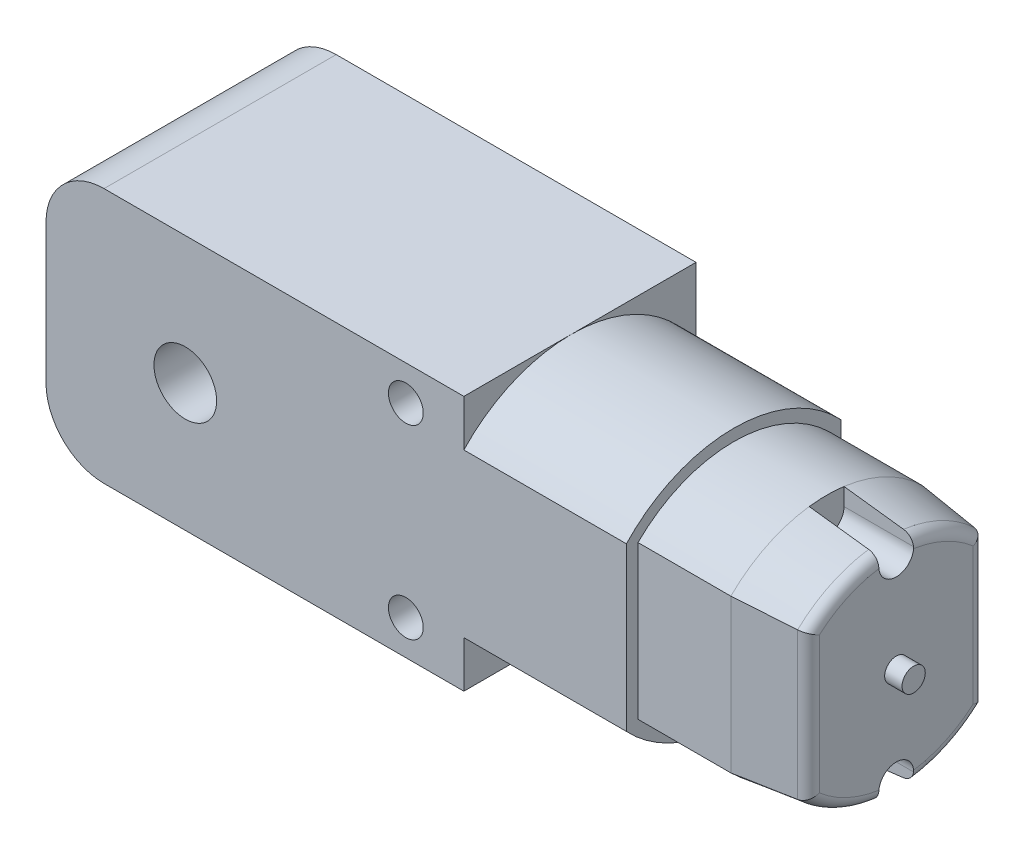
SolidWorks part; units mm, degrees
ref_plane "Alzado" through (0, 0, 0) normal (0, 0, 1) x (1, 0, 0)
ref_plane "Planta" through (0, 0, 0) normal (0, 1, 0) x (1, 0, 0)
ref_plane "Vista lateral" through (0, 0, 0) normal (1, 0, 0) x (0, 0, -1)
sketch "Croquis1" plane through (0, 0, 0) normal (0, 1, 0) x (1, 0, 0)
  line L1 (-25, -10) -> (25, -10)
  line L2 (-25, -10) -> (-25, 10)
  line L3 (-25, 10) -> (25, 10)
  line L4 (25, -10) -> (25, 10)
  line L5 (-25, -10) -> (25, 10) construction
  line L6 (-25, 10) -> (25, -10) construction
  point P0 (0, 0)
  dimension "D1" = 50
  dimension "D2" = 20
extrude "Saliente-Extruir1" add sketch "Croquis1" along normal mid plane 22
fillet "Redondeo1" radius 5 2 edges at (-25, -11, 0) (-25, 11, 0)
sketch "Croquis2" plane through (25, 0, 0) normal (1, 0, 0) x (0, 0, -1)
  line L0 (-10, 11) -> (-10, -11) construction
  line L2 (-10, 7) -> (-10, -7)
  line L3 (8.5, 7) -> (8.5, -7)
  line L4 (10, 11) -> (10, -11) construction
  line L5 (-10, 11) -> (10, 11) construction
  line L6 (-10, -11) -> (10, -11) construction
  arc A0 (-10, 7) -> (8.5, 7) centre (-0.75, -1.6953) cw
  arc A1 (-10, -7) -> (8.5, -7) centre (-0.75, 1.6953) ccw
  dimension "D1" = 1.5
  dimension "D2" = 4
  dimension "D3" = 4
  dimension "D4" = 4
  dimension "D5" = 4
extrude "Cortar-Extruir1" cut sketch "Croquis2" against normal blind 14 flip side to cut
sketch "Croquis3" plane through (0, 0, -10) normal (0, 0, -1) x (-1, 0, 0)
  line L0 (-11, 11) -> (-11, 7) construction
  line L1 (-11, 11) -> (20, 11) construction
  line L2 (11, 0) -> (-11, 0) construction
  circle A0 centre (-6, 8) radius 1.5
  circle A1 centre (-6, -8) radius 1.5
  dimension "D1" = 3
  dimension "D2" = 5
  dimension "D3" = 3
extrude "Cortar-Extruir2" cut sketch "Croquis3" against normal through all
sketch "Croquis8" plane through (25, 0, 0) normal (1, 0, 0) x (0, 0, -1)
  line L4 (-9, 6.5943) -> (-9, -6.5943)
  line L5 (7.5, -6.5943) -> (7.5, 6.5943)
  line L6 (-9, 6.5943) -> (-9, -6.5943)
  line L7 (7.5, -6.5943) -> (7.5, 6.5943)
  arc A4 (7.5, 6.5943) -> (-9, 6.5943) centre (-0.75, -1.6953) ccw
  arc A5 (-9, -6.5943) -> (7.5, -6.5943) centre (-0.75, 1.6953) ccw
  arc A6 (7.5, 6.5943) -> (-9, 6.5943) centre (-0.75, -1.6953) ccw
  arc A7 (-9, -6.5943) -> (7.5, -6.5943) centre (-0.75, 1.6953) ccw
  dimension "D1" = 1
extrude "Saliente-Extruir6" add sketch "Croquis8" along normal blind 8
sketch "Croquis9" plane through (0, 0, 10) normal (0, 0, 1) x (1, 0, 0)
  line L0 (-20, 11) -> (11, 11) construction
  line L1 (-25, 6) -> (-25, -6) construction
  circle A0 centre (-13, 0) radius 2.7
  dimension "D3" = 5.4
  dimension "D1" = 11
  dimension "D2" = 12
extrude "Cortar-Extruir5" cut sketch "Croquis9" against normal through all
sketch "Croquis11" plane through (33, 0, 0) normal (1, 0, 0) x (0, 0, -1)
  line L2 (-9, 6.5943) -> (-9, -6.5943)
  line L3 (7.5, -6.5943) -> (7.5, 6.5943)
  line L4 (-9, 6.5943) -> (-9, -6.5943)
  line L5 (7.5, -6.5943) -> (7.5, 6.5943)
  arc A2 (7.5, 6.5943) -> (-9, 6.5943) centre (-0.75, -1.6953) ccw
  arc A3 (-9, -6.5943) -> (7.5, -6.5943) centre (-0.75, 1.6953) ccw
  arc A4 (7.5, 6.5943) -> (-9, 6.5943) centre (-0.75, -1.6953) ccw
  arc A5 (-9, -6.5943) -> (7.5, -6.5943) centre (-0.75, 1.6953) ccw
  dimension "D1" = 0
extrude "Saliente-Extruir7" add sketch "Croquis11" along normal blind 6 draft 7
fillet "Redondeo2" radius 1 4 edges at (39, 0, -6.7633) (39, -9.2633, 0.75) (39, 0, 8.2633) (39, 9.2633, 0.75)
sketch "Croquis12" plane through (39, 0, 0) normal (1, 0, 0) x (0, 0, -1)
  line L0 (2.8786, 3.44) -> (2.8786, -3.44)
  line L1 (5.8786, -5.8905) -> (5.8786, 5.8905) construction
  line L3 (-3.75, 2) -> (-2.75, 2)
  line L4 (-3.75, 2) -> (-3.75, -2)
  line L5 (-3.75, -2) -> (-2.75, -2)
  line L6 (-2.75, 2) -> (-2.75, -2)
  arc A0 (2.8786, 3.44) -> (2.8786, -3.44) centre (-0.75, 0) ccw
  arc A1 (5.8786, 5.8905) -> (-7.3786, 5.8905) centre (-0.75, -1.6953) ccw construction
  point P6 (-0.75, 8.3786)
  point P9 (5.8786, 0)
  point P14 (-2.75, 0)
  dimension "D1" = 5
  dimension "D2" = 3
  dimension "D3" = 1
  dimension "D4" = 4
  dimension "D5" = 2
sketch "Croquis14" plane through (39, 0, 0) normal (1, 0, 0) x (0, 0, -1)
  line L0 (-2.25, 9.9034) -> (-2.25, 8.4034)
  line L1 (0.75, 8.4034) -> (0.75, 9.9034)
  line L2 (11, 0) -> (-11, 0) construction
  line L3 (-2.25, -9.9034) -> (-2.25, -8.4034)
  line L4 (0.75, -8.4034) -> (0.75, -9.9034)
  arc A0 (7.5, 6.5943) -> (-9, 6.5943) centre (-0.75, -1.6953) ccw construction
  arc A1 (-2.25, 8.4034) -> (0.75, 8.4034) centre (-0.75, 8.4034) ccw
  arc A2 (0.75, 9.9034) -> (-2.25, 9.9034) centre (-0.75, -1.6953) ccw
  arc A3 (0.75, -9.9034) -> (-2.25, -9.9034) centre (-0.75, 1.6953) cw
  arc A4 (-2.25, -8.4034) -> (0.75, -8.4034) centre (-0.75, -8.4034) cw
  dimension "D1" = 3
  dimension "D2" = 1.5
  dimension "D3" = 1.5
extrude "Cortar-Extruir6" cut sketch "Croquis14" against normal blind 6
sketch "Croquis15" plane through (-25, 0, 0) normal (-1, 0, 0) x (0, 0, 1)
  line L1 (-1, -2.5) -> (1, -2.5)
  line L2 (-1, -2.5) -> (-1, 2.5)
  line L3 (-1, 2.5) -> (1, 2.5)
  line L4 (1, -2.5) -> (1, 2.5)
  line L5 (-1, -2.5) -> (1, 2.5) construction
  line L6 (-1, 2.5) -> (1, -2.5) construction
  point P0 (0, 0)
  dimension "D1" = 2
  dimension "D2" = 5
extrude "Saliente-Extruir10" add sketch "Croquis15" along normal blind 5.5
sketch "Croquis16" plane through (0, 0, 1) normal (0, 0, 1) x (1, 0, 0)
  line L0 (-30.5, 2.5) -> (-25, 2.5) construction
  circle A0 centre (-27.75, 0) radius 1.5
  point P4 (-27.75, 2.5)
  dimension "D1" = 3
extrude "Cortar-Extruir7" cut sketch "Croquis16" against normal through all
sketch "Croquis17" plane through (39, 0, 0) normal (1, 0, 0) x (0, 0, -1)
  circle A0 centre (-0.75, 0) radius 1
  dimension "D1" = 2
extrude "Saliente-Extruir11" add sketch "Croquis17" along normal blind 1.5
sketch "Croquis18" plane through (-30.5, 0, 0) normal (-1, 0, 0) x (0, 0, 1)
  line L4 (1, -2.5) -> (1, 2.5)
  line L5 (1, 2.5) -> (-1, 2.5)
  line L6 (-1, 2.5) -> (-1, -2.5)
  line L7 (-1, -2.5) -> (1, -2.5)
  line L8 (1, -2.5) -> (1, 2.5)
  line L9 (1, 2.5) -> (-1, 2.5)
  line L10 (-1, 2.5) -> (-1, -2.5)
  line L11 (-1, -2.5) -> (1, -2.5)
  dimension "D1" = 0
extrude "Cortar-Extruir8" cut sketch "Croquis18" along normal through all from surface starting at face at (-25, 0, 0)
